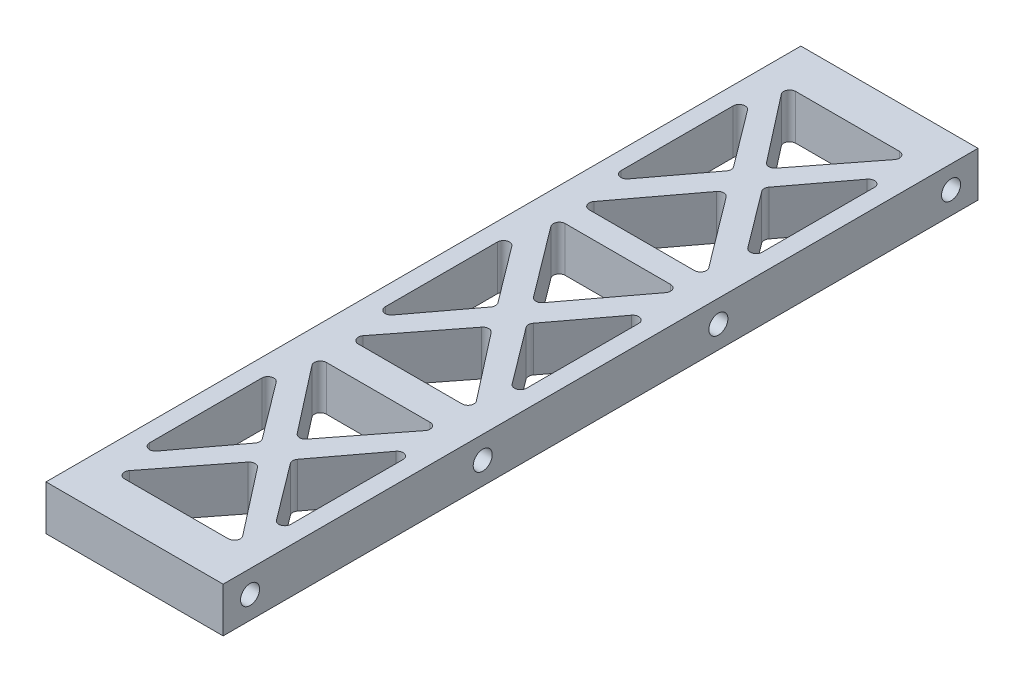
SolidWorks part; units mm, degrees
ref_plane "Front Plane" through (0, 0, 0) normal (0, 0, 1) x (1, 0, 0)
ref_plane "Top Plane" through (0, 0, 0) normal (0, 1, 0) x (1, 0, 0)
ref_plane "Right Plane" through (0, 0, 0) normal (1, 0, 0) x (0, 0, -1)
sketch "Sketch1" plane through (0, 0, 0) normal (0, 1, 0) x (1, 0, 0)
  line L0 (-757.9313, 25.0133) -> (-720.3313, 25.0133) construction
  line L1 (-757.9313, 75.04) -> (-720.3313, 75.04)
  line L2 (-757.9313, 75.04) -> (-757.9313, -75.04)
  line L3 (-757.9313, -75.04) -> (-720.3313, -75.04)
  line L4 (-720.3313, 75.04) -> (-720.3313, -75.04)
  line L5 (-757.9313, -25.0133) -> (-720.3313, -25.0133) construction
  line L6 (-757.9313, 25.0133) -> (-720.3313, 75.04) construction
  line L7 (-757.9313, 75.04) -> (-720.3313, 25.0133) construction
  line L8 (-757.9313, 25.0133) -> (-720.3313, -25.0133) construction
  line L9 (-720.3313, -25.0133) -> (-757.9313, -25.0133)
  line L10 (-757.9313, -25.0133) -> (-720.3313, 25.0133) construction
  line L11 (-757.9313, -25.0133) -> (-720.3313, -75.04) construction
  line L12 (-720.3313, -25.0133) -> (-757.9313, -75.04) construction
  dimension "D1" = 150.08
  dimension "D2" = 37.6
  dimension "D3" = 75.04
  dimension "D4" = 50.0267
  dimension "D5" = 50.0267
extrude "Boss-Extrude1" add sketch "Sketch1" along normal blind 9.525 contours L4 L9 L2 L3 | L9 L4 L1 L2 region at (-739.1313, 0, -25.0133) region at (-739.1313, 0, 50.0267)
sketch "Sketch3" plane through (0, 9.525, 0) normal (0, 1, 0) x (1, 0, 0)
  line L0 (-740.1466, 44.4483) -> (-751.3168, 29.5864)
  line L1 (-750.3016, 27.5533) -> (-727.9611, 27.5533)
  line L2 (-726.9459, 29.5864) -> (-738.1161, 44.4483)
  line L3 (-757.9313, 25.0133) -> (-720.3313, 75.04) construction
  line L4 (-757.9313, 75.04) -> (-720.3313, 25.0133) construction
  line L5 (-757.9313, 25.0133) -> (-720.3313, 25.0133) construction
  line L6 (-757.9313, 25.0133) -> (-720.3313, 25.0133) construction
  line L7 (-750.3016, 22.4733) -> (-727.9611, 22.4733)
  line L8 (-740.1466, 5.5783) -> (-751.3168, 20.4403)
  line L9 (-726.9459, 20.4403) -> (-738.1161, 5.5783)
  line L10 (-757.9313, 25.0133) -> (-720.3313, 75.04) construction
  line L11 (-757.9313, 75.04) -> (-720.3313, 25.0133) construction
  line L12 (-751.8361, 62.7028) -> (-742.8823, 50.7897)
  line L13 (-742.8823, 49.2636) -> (-751.8361, 37.3506)
  line L14 (-750.1403, 71.23) -> (-728.1224, 71.23)
  line L15 (-740.1337, 55.0286) -> (-751.1427, 69.1802)
  line L16 (-727.12, 69.1802) -> (-738.1289, 55.0286)
  line L17 (-757.9313, -25.0133) -> (-720.3313, -25.0133) construction
  line L18 (-720.3313, -25.0133) -> (-739.1313, 0) construction
  line L19 (-757.9313, 25.0133) -> (-720.3313, -25.0133) construction
  line L20 (-739.1313, 0) -> (-757.9313, -25.0133) construction
  line L21 (-720.3313, 25.0133) -> (-739.1313, 0) construction
  line L22 (-757.9313, 25.0133) -> (-739.1313, 0) construction
  line L23 (-754.1213, 38.1136) -> (-754.1213, 61.9397)
  line L24 (-739.1313, 72.5) -> (-739.1313, -49927.5) construction
  line L25 (-757.9313, 75.04) -> (-720.3313, 75.04) construction
  line L26 (-757.9313, -25.0133) -> (-720.3313, -75.04) construction
  line L27 (-720.3313, -25.0133) -> (-757.9313, -75.04) construction
  line L28 (-740.1337, -5.4252) -> (-751.1427, -19.5769)
  line L29 (-727.12, -19.5769) -> (-738.1289, -5.4252)
  line L30 (-750.1403, -21.6267) -> (-728.1224, -21.6267)
  line L31 (-727.12, -30.4498) -> (-738.1289, -44.6014)
  line L32 (-750.1403, -28.4) -> (-728.1224, -28.4)
  line L33 (-740.1337, -44.6014) -> (-751.1427, -30.4498)
  line L34 (-757.9313, 75.04) -> (-757.9313, -75.04) construction
  line L35 (-750.1403, -71.23) -> (-728.1224, -71.23)
  line L36 (-740.1337, -55.0286) -> (-751.1427, -69.1802)
  line L37 (-727.12, -69.1802) -> (-738.1289, -55.0286)
  line L38 (-754.1213, 11.9131) -> (-754.1213, -11.9131)
  line L39 (-742.8823, 0.763) -> (-751.8361, 12.6761)
  line L40 (-751.8361, -12.6761) -> (-742.8823, -0.763)
  line L41 (-742.8823, -50.7897) -> (-751.8361, -62.7028)
  line L42 (-751.8361, -37.3506) -> (-742.8823, -49.2636)
  line L43 (-754.1213, -61.9397) -> (-754.1213, -38.1136)
  line L44 (-726.4266, -37.3506) -> (-735.3804, -49.2636)
  line L45 (-724.1413, -61.9397) -> (-724.1413, -38.1136)
  line L46 (-735.3804, -50.7897) -> (-726.4266, -62.7028)
  line L47 (-735.3804, 0.763) -> (-726.4266, 12.6761)
  line L48 (-726.4266, -12.6761) -> (-735.3804, -0.763)
  line L49 (-724.1413, 11.9131) -> (-724.1413, -11.9131)
  line L50 (-724.1413, 38.1136) -> (-724.1413, 61.9397)
  line L51 (-735.3804, 49.2636) -> (-726.4266, 37.3506)
  line L52 (-726.4266, 62.7028) -> (-735.3804, 50.7897)
  line L53 (-757.9313, -75.04) -> (-720.3313, -75.04) construction
  arc A0 (-728.1224, -71.23) -> (-727.12, -69.1802) centre (-728.1224, -69.96) ccw
  arc A1 (-750.1403, -71.23) -> (-751.1427, -69.1802) centre (-750.1403, -69.96) cw
  arc A2 (-740.1337, -55.0286) -> (-738.1289, -55.0286) centre (-739.1313, -55.8084) cw
  arc A3 (-724.1413, -61.9397) -> (-726.4266, -62.7028) centre (-725.4113, -61.9397) cw
  arc A4 (-726.4266, -37.3506) -> (-724.1413, -38.1136) centre (-725.4113, -38.1136) cw
  arc A5 (-735.3804, -49.2636) -> (-735.3804, -50.7897) centre (-734.3652, -50.0267) ccw
  arc A6 (-742.8823, -50.7897) -> (-742.8823, -49.2636) centre (-743.8975, -50.0267) ccw
  arc A7 (-751.8361, -62.7028) -> (-754.1213, -61.9397) centre (-752.8513, -61.9397) cw
  arc A8 (-751.8361, -37.3506) -> (-754.1213, -38.1136) centre (-752.8513, -38.1136) ccw
  arc A9 (-750.1403, -28.4) -> (-751.1427, -30.4498) centre (-750.1403, -29.67) ccw
  arc A10 (-738.1289, -44.6014) -> (-740.1337, -44.6014) centre (-739.1313, -43.8216) cw
  arc A11 (-727.12, -30.4498) -> (-728.1224, -28.4) centre (-728.1224, -29.67) ccw
  arc A12 (-727.12, -19.5769) -> (-728.1224, -21.6267) centre (-728.1224, -20.3567) cw
  arc A13 (-751.1427, -19.5769) -> (-750.1403, -21.6267) centre (-750.1403, -20.3567) ccw
  arc A14 (-740.1337, -5.4252) -> (-738.1289, -5.4252) centre (-739.1313, -6.2051) cw
  arc A15 (-735.3804, 0.763) -> (-735.3804, -0.763) centre (-734.3652, 0) ccw
  arc A16 (-726.4266, -12.6761) -> (-724.1413, -11.9131) centre (-725.4113, -11.9131) ccw
  arc A17 (-754.1213, -11.9131) -> (-751.8361, -12.6761) centre (-752.8513, -11.9131) ccw
  arc A18 (-742.8823, 0.763) -> (-742.8823, -0.763) centre (-743.8975, 0) cw
  arc A19 (-754.1213, 11.9131) -> (-751.8361, 12.6761) centre (-752.8513, 11.9131) cw
  arc A20 (-750.3016, 22.4733) -> (-751.3168, 20.4403) centre (-750.3016, 21.2033) ccw
  arc A21 (-740.1466, 5.5783) -> (-738.1161, 5.5783) centre (-739.1313, 6.3414) ccw
  arc A22 (-727.9611, 22.4733) -> (-726.9459, 20.4403) centre (-727.9611, 21.2033) cw
  arc A23 (-726.4266, 12.6761) -> (-724.1413, 11.9131) centre (-725.4113, 11.9131) cw
  arc A24 (-727.9611, 27.5533) -> (-726.9459, 29.5864) centre (-727.9611, 28.8233) ccw
  arc A25 (-740.1466, 44.4483) -> (-738.1161, 44.4483) centre (-739.1313, 43.6853) cw
  arc A26 (-751.3168, 29.5864) -> (-750.3016, 27.5533) centre (-750.3016, 28.8233) ccw
  arc A27 (-751.8361, 37.3506) -> (-754.1213, 38.1136) centre (-752.8513, 38.1136) cw
  arc A28 (-742.8823, 50.7897) -> (-742.8823, 49.2636) centre (-743.8975, 50.0267) cw
  arc A29 (-751.8361, 62.7028) -> (-754.1213, 61.9397) centre (-752.8513, 61.9397) ccw
  arc A30 (-726.4266, 62.7028) -> (-724.1413, 61.9397) centre (-725.4113, 61.9397) cw
  arc A31 (-724.1413, 38.1136) -> (-726.4266, 37.3506) centre (-725.4113, 38.1136) cw
  arc A32 (-735.3804, 49.2636) -> (-735.3804, 50.7897) centre (-734.3652, 50.0267) cw
  arc A33 (-740.1337, 55.0286) -> (-738.1289, 55.0286) centre (-739.1313, 55.8084) ccw
  arc A34 (-728.1224, 71.23) -> (-727.12, 69.1802) centre (-728.1224, 69.96) cw
  arc A35 (-750.1403, 71.23) -> (-751.1427, 69.1802) centre (-750.1403, 69.96) ccw
  point P51 (-739.1313, 75.04)
  point P78 (-724.1413, -65.7432)
  point P81 (-724.1413, -34.3101)
  point P84 (-735.9539, -50.0267)
  point P87 (-742.3088, -50.0267)
  point P90 (-754.1213, -65.7432)
  point P93 (-754.1213, -34.3101)
  point P96 (-752.7373, -28.4)
  point P99 (-739.1313, -45.89)
  point P102 (-725.5254, -28.4)
  point P105 (-725.5254, -21.6267)
  point P108 (-752.7373, -21.6267)
  point P111 (-739.1313, -4.1367)
  point P114 (-735.9539, 0)
  point P117 (-724.1413, -15.7166)
  point P120 (-754.1213, -15.7166)
  point P123 (-742.3088, 0)
  point P126 (-754.1213, 15.7166)
  point P129 (-752.8448, 22.4733)
  point P132 (-739.1313, 4.2276)
  point P135 (-725.4178, 22.4733)
  point P138 (-724.1413, 15.7166)
  point P141 (-725.4178, 27.5533)
  point P144 (-739.1313, 45.7991)
  point P147 (-752.8448, 27.5533)
  point P150 (-754.1213, 34.3101)
  point P153 (-742.3088, 50.0267)
  point P156 (-754.1213, 65.7432)
  point P159 (-724.1413, 65.7432)
  point P162 (-724.1413, 34.3101)
  point P165 (-735.9539, 50.0267)
  dimension "D9" = 1.27
  dimension "D1" = 2.54
  dimension "D2" = 2.54
  dimension "D3" = 2.54
  dimension "D4" = 2.54
  dimension "D5" = 3.81
  dimension "D6" = 2.54
  dimension "D7" = 3.81
  dimension "D8" = 3.81
extrude "Cut-Extrude1" cut sketch "Sketch3" against normal through all
sketch "Sketch7" plane through (0, 0, 75.04) normal (0, 0, 1) x (1, 0, 0)
  line L0 (-757.9313, 0) -> (-720.3313, 0) construction
  line L1 (-757.9313, 9.525) -> (-720.3313, 9.525)
  line L2 (-757.9313, 9.525) -> (-757.9313, 0)
  line L3 (-757.9313, 0) -> (-720.3313, 0)
  line L4 (-720.3313, 9.525) -> (-720.3313, 0)
extrude "Boss-Extrude3" add sketch "Sketch7" along normal blind 2.54
sketch "Sketch8" plane through (0, 0, -75.04) normal (0, 0, -1) x (-1, 0, 0)
  line L1 (720.3313, 9.525) -> (757.9313, 9.525)
  line L2 (720.3313, 9.525) -> (720.3313, 0)
  line L3 (720.3313, 0) -> (757.9313, 0)
  line L4 (757.9313, 9.525) -> (757.9313, 0)
extrude "Boss-Extrude4" add sketch "Sketch8" along normal blind 2.54
sketch "Sketch5" plane through (-720.3313, 0, 0) normal (1, 0, 0) x (0, 0, -1)
  line L0 (-77.58, 0) -> (-77.58, 9.525) construction
  line L1 (77.58, 9.525) -> (77.58, 0) construction
  line L2 (200072.5, 9.525) -> (-249927.5, 9.525) construction
  circle A0 centre (-74.405, 4.7625) radius 2.413
  circle A1 centre (-25.0133, 4.7625) radius 2.413
  circle A2 centre (25.0133, 4.7625) radius 2.413
  circle A3 centre (74.405, 4.7625) radius 2.413
  dimension "D1" = 4.826
  dimension "D2" = 4.826
  dimension "D3" = 4.826
  dimension "D4" = 3.175
  dimension "D5" = 3.175
  dimension "D6" = 4.7625
ref_plane "Plane2" through (-739.1313, 0, 0) normal (-1, 0, 0) x (0, 0, 1)
hole_wizard "#10-32 Tapped Hole1" positions "Sketch9" profile "Sketch11" tap size "#10-32" standard "ANSI Inch"
sketch "Sketch9" plane through (-720.3313, 0, 0) normal (1, 0, 0) x (0, 0, -1)
  point P0 (-74.405, 4.7625)
  point P3 (-25.0133, 4.7625)
  point P6 (25.0133, 4.7625)
  point P8 (74.405, 4.7625)
  point P11 (25.0133, 4.7625)
  point P13 (74.405, 4.7625)
cosmetic thread "Hole Thread2" parameters "D1"=9.652, "D2"=4.826
sketch "Sketch11" plane through (-720.3313, 4.7625, 74.405) normal (0, 1, 0) x (0, 0, -1)
  line L0 (0, 0) -> (0, 14.9293)
  line L1 (0, 14.9293) -> (2.0193, 13.716)
  line L2 (2.0193, 13.716) -> (2.0193, 0)
  line L5 (2.0193, 0) -> (0, 0)
  line L10 (0, 14.9293) -> (-2.0193, 13.716) construction
  line L11 (0, -6.35) -> (0, 107.95) construction
  dimension "Tap Drill Dia." = 4.0386
  dimension "Tap Drill Depth" = 13.716
  dimension "Drill Angle" = 118
cosmetic thread "Hole Thread5" parameters "D1"=9.652, "D2"=4.826
cosmetic thread "Hole Thread6" parameters "D1"=9.652, "D2"=4.826
cosmetic thread "Hole Thread7" parameters "D1"=9.652, "D2"=4.826
mirror "Mirror1" about plane through (-739.1313, 0, 0) normal (-1, 0, 0) of "#10-32 Tapped Hole1"
cosmetic thread "Hole Thread8" parameters "D1"=9.652, "D2"=4.826
cosmetic thread "Hole Thread9" parameters "D1"=9.652, "D2"=4.826
cosmetic thread "Hole Thread10" parameters "D1"=9.652, "D2"=4.826
cosmetic thread "Hole Thread11" parameters "D1"=9.652, "D2"=4.826
sketch "Sketch12" plane through (0, 0, -77.58) normal (0, 0, -1) x (-1, 0, 0)
  line L1 (720.3313, 9.525) -> (757.9313, 9.525)
  line L2 (720.3313, 9.525) -> (720.3313, 0)
  line L3 (720.3313, 0) -> (757.9313, 0)
  line L4 (757.9313, 9.525) -> (757.9313, 0)
extrude "Boss-Extrude7" add sketch "Sketch12" along normal blind 2.54
sketch "Sketch13" plane through (0, 0, 77.58) normal (0, 0, 1) x (1, 0, 0)
  line L0 (-720.3313, 9.525) -> (-757.9313, 9.525) construction
  line L1 (-757.9313, 9.525) -> (-720.3313, 9.525)
  line L2 (-757.9313, 9.525) -> (-757.9313, 0)
  line L3 (-757.9313, 0) -> (-720.3313, 0)
  line L4 (-720.3313, 9.525) -> (-720.3313, 0)
  line L5 (-757.9313, 9.525) -> (-720.3313, 9.525) construction
  line L6 (-757.9313, 0) -> (-720.3313, 0) construction
  line L7 (-757.9313, 0) -> (-720.3313, 0) construction
extrude "Boss-Extrude8" add sketch "Sketch13" along normal blind 2.54
